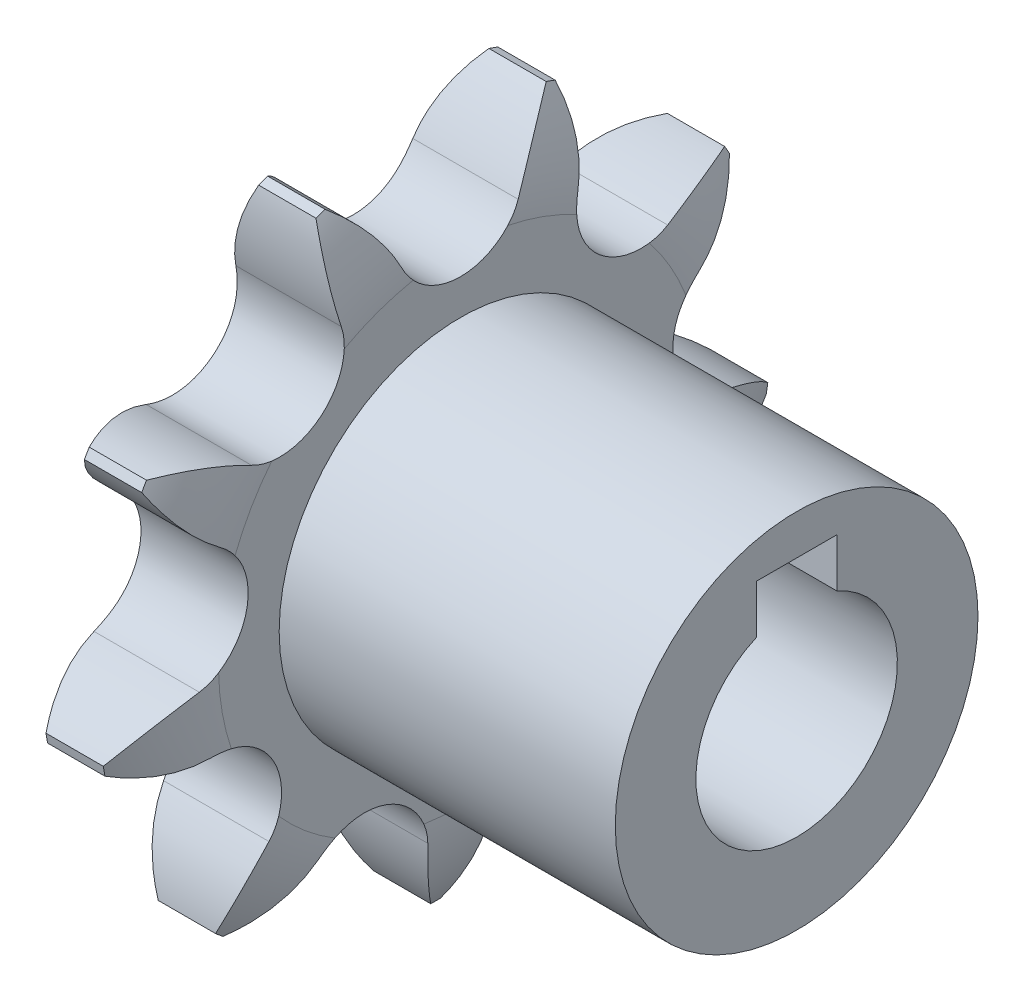
SolidWorks part; units mm, degrees
ref_plane "Plane1" through (0, 0, 0) normal (0, 0, 1) x (1, 0, 0)
ref_plane "Plane2" through (0, 0, 0) normal (0, 1, 0) x (1, 0, 0)
ref_plane "Plane3" through (0, 0, 0) normal (1, 0, 0) x (0, 0, -1)
sketch "Clipboard" plane through (0, 0, 0) normal (0, 1, 0) x (1, 0, 0)
  line L0 (0, 0) -> (9.4077, -1.49)
  line L1 (-15, 0) -> (100, 0) construction
  line L2 (0, 0) -> (-0.8203, 0.9272)
  line L3 (0, 0) -> (-8.8973, 3.4006)
  line L4 (0, 0) -> (3.0618, 0.4849)
  line L5 (0, 0) -> (-46.8476, -17.4728)
  line L6 (0, 0) -> (-4.4098, -2.9753)
  line L7 (-0.8203, 0.9272) -> (48.4205, 9.6097)
  line L8 (-76.2, 38.1) -> (-74.4, 38.1)
  line L9 (-73.3242, 40.7328) -> (-72.926, 40.7699)
  line L10 (-73.4529, 9.1872) -> (-63.2129, 9.1872)
  circle A0 centre (0, 0) radius 3.175
  circle A1 centre (0, 0) radius 8.4097
  circle A2 centre (0, 0) radius 37.5
  dimension "Num_teeth" = 9
  dimension "Thickness" = 5.3196
sketch "BasProSke" plane through (0, 0, 0) normal (0, 1, 0) x (1, 0, 0)
  line L0 (-10, 0) -> (60, 0) construction
  line L1 (0, 0) -> (0, 12.0069)
  line L2 (0, 0) -> (5.3196, 0)
  line L3 (5.3196, 0) -> (5.3196, 12.0069)
  line L4 (4.0816, 16.7027) -> (1.238, 16.7027)
  arc A0 (0, 12.0069) -> (1.238, 16.7027) centre (9.525, 12.0069) cw
  arc A1 (5.3196, 12.0069) -> (4.0816, 16.7027) centre (-4.2054, 12.0069) ccw
  dimension "D1" = 9.525
  dimension "Thickness" = 5.3196
  dimension "Diameter" = 33.4055
revolve "Base-Revolve" add sketch "BasProSke" angle 360 about L0
sketch "TooCutSke" plane through (0, 0, 0) normal (1, 0, 0) x (0, 0, -1)
  line L0 (0, 13.9564) -> (2.9063, 12.6011) construction
  line L1 (0, 0) -> (0, 107) construction
  line L2 (0, 13.9564) -> (-10, 13.9564) construction
  line L3 (0, 13.9564) -> (-2.9063, 12.6011) construction
  arc A0 (2.9063, 12.6011) -> (5.9941, 16.1247) centre (10.503, 9.0588) cw
  arc A1 (2.9063, 12.6011) -> (-2.9063, 12.6011) centre (0, 13.9564) cw
  arc A2 (-2.9063, 12.6011) -> (-5.9941, 16.1247) centre (-10.503, 9.0588) ccw
  arc A3 (5.9941, 16.1247) -> (-5.9941, 16.1247) centre (0, 0) ccw
extrude "ToothCut" cut sketch "TooCutSke" along normal through all
pattern_circular "TeethCuts" count 9 every 40 about axis through (-10, 0, 0) along (1, 0, 0) of "ToothCut"
sketch "HubNeaOneSke" plane through (0, 0, 0) normal (-1, 0, 0) x (0, 0, 1)
  circle A0 centre (0, 0) radius 8.4097
  dimension "Diameter" = 16.8193
extrude "HubNearOne" [suppressed] add sketch "HubNeaOneSke" along normal blind 44.6809
fillet "HubNearOneFillet" [suppressed] radius 0.4
sketch "HubNeaBotSke" plane through (0, 0, 0) normal (-1, 0, 0) x (0, 0, 1)
  circle A0 centre (0, 0) radius 8.4097
  dimension "Diameter" = 16.8193
extrude "HubNearBoth" [suppressed] add sketch "HubNeaBotSke" along normal blind 22.3405
fillet "HubNearBothFillet" [suppressed] radius 0.4
ref_plane "FarPln" through (5.3196, 0, 0) normal (1, 0, 0) x (0, 0, -1)
sketch "HubFarSke" plane through (5.3196, 0, 0) normal (1, 0, 0) x (0, 0, -1)
  circle A0 centre (0, 0) radius 8.4097
  dimension "Diameter" = 16.8193
extrude "HubFar" [suppressed] add sketch "HubFarSke" along normal blind 22.3405
fillet "HubFarFillet" [suppressed] radius 0.4
sketch "BorSke" plane through (0, 0, 0) normal (1, 0, 0) x (0, 0, -1)
  circle A0 centre (0, 0) radius 5
  dimension "Diameter" = 10
extrude "Bore" cut sketch "BorSke" along normal mid plane 100.001
sketch "KeySke" plane through (0, 0, 0) normal (1, 0, 0) x (0, 0, -1)
  line L0 (-2, 0) -> (-2, 6.8)
  line L1 (-2, 6.8) -> (2, 6.8)
  line L2 (2, 6.8) -> (2, 0)
  line L3 (0, 0) -> (0, 34) construction
  line L4 (-2, 0) -> (2, 0)
  dimension "Width" = 4
extrude "Keyway" [suppressed] cut sketch "KeySke" along normal mid plane 100.001
pattern_circular "Keyway2" [suppressed] count 2 every 90 about axis through (-10, 0, 0) along (1, 0, 0)
sketch "Sketch1" plane through (5.3196, 0, 0) normal (1, 0, 0) x (0, 0, -1)
  circle A0 centre (0, 0) radius 9
  circle A1 centre (0, 0) radius 3
  dimension "D1" = 18
  dimension "D2" = 6
extrude "Boss-Extrude1" add sketch "Sketch1" along normal offset from surface (16.6804 mm away) 22 up to face at (0, 0, -5)
sketch "Sketch2" plane through (0, 0, 0) normal (1, 0, 0) x (0, 0, -1)
  circle A0 centre (0, 0) radius 5
  dimension "D1" = 10
extrude "Cut-Extrude1" cut sketch "Sketch2" along normal blind 24
sketch "Sketch3" plane through (0, 0, 0) normal (-1, 0, 0) x (0, 0, 1)
  line L0 (-2, 7) -> (-2, 3)
  line L1 (-2, 7) -> (2, 7)
  line L2 (-2, 3) -> (2, 3)
  line L3 (2, 7) -> (2, 3)
  line L4 (-2, 7) -> (2, 3) construction
  line L5 (-2, 3) -> (2, 7) construction
  line L6 (0, 0) -> (0, 5) construction
  circle A0 centre (0, 0) radius 5 construction
  point P1 (0, 5)
  dimension "D1" = 4
  dimension "D2" = 4
extrude "Cut-Extrude2" cut sketch "Sketch3" against normal through all
equation "' \"Pitch@Clipboard\" = 12.7"
equation "' \"Num_strands@Clipboard\" = 1"
equation "' \"Num_teeth@Clipboard\" = 9"
equation "' \"Hub_dia@Clipboard\" = 50"
equation "' \"Overall_len@Clipboard\" = 3"
equation "' \"Diameter@BorSke\" = 12"
equation "' \"T_dim@Clipboard\" = 1"
equation "' \"Width@KeySke\" = 2"
equation "' \"Dr@Clipboard\" = 8.51"
equation "' \"Face_width@Clipboard\" = 7.2"
equation "' \"Side_radius@Clipboard\" = 12.7"
equation "' \"Side_relief@Clipboard\" = 1.27"
equation "' \"Transv_pitch@Clipboard\" = 13.92"
equation "' \"Show_teeth@Clipboard\" = 9"
equation "' \"Fillet_rad@Clipboard\" = 0.6"
equation "' \"Plate_wid@Clipboard\" = 11.8"
equation "\"Num_teeth@Clipboard\" = int( \"Num_teeth@Clipboard\" )"
equation "\"Num_teeth@Clipboard\" = ((sgn( \"Num_teeth@Clipboard\" - 5.0)+1)*( \"Num_teeth@Clipboard\" - 5.0))/2 +5.0"
equation "\"Num_teeth@Clipboard\" = ((sgn( \"Num_teeth@Clipboard\" - 200.0)-1)*( \"Num_teeth@Clipboard\" - 200.0))/-2 +200.0"
equation "\"MHD@Clipboard\" = \"Pitch@Clipboard\" * (1.0 / tan(3.14159265 / \"Num_teeth@Clipboard\" )) - 1.04 * \"Plate_wid@Clipboard\" - 0.76"
equation "\"Thickness@Clipboard\"  = \"Face_width@Clipboard\" + (\"Num_strands@Clipboard\" - 1) * \"Transv_pitch@Clipboard\""
equation "\"OAL@Clipboard\" = \"Thickness@Clipboard\" + 2 * \"Fillet_rad@Clipboard\" + 1"
equation "\"MHD@Clipboard\" = ((sgn( \"MHD@Clipboard\" - \"Hub_dia@Clipboard\" )-1)*( \"MHD@Clipboard\" - \"Hub_dia@Clipboard\" ))/-2+ \"Hub_dia@Clipboard\""
equation "\"OAL@Clipboard\" = ((sgn( \"OAL@Clipboard\" - \"Overall_len@Clipboard\" )+1)*( \"OAL@Clipboard\" - \"Overall_len@Clipboard\" ))/2 + \"Overall_len@Clipboard\" + 0.0005"
equation "\"Num_teeth@TeethCuts\" = int( \"Show_teeth@Clipboard\" ) + 1"
equation "\"Num_teeth@TeethCuts\" = ((sgn( \"Num_teeth@TeethCuts\" - \"Num_teeth@Clipboard\" )-1)*( \"Num_teeth@TeethCuts\" - \"Num_teeth@Clipboard\" ))/-2+ \"Num_teeth@Clipboard\""
equation "\"Num_teeth@TeethCuts\" = ((sgn( \"Num_teeth@TeethCuts\" - 2.0)+1)*( \"Num_teeth@TeethCuts\" - 2.0))/2 +2.0"
equation "\"Angle@TeethCuts\" = 360.0 / \"Num_teeth@Clipboard\""
equation "\"Seat_radius@TooCutSke\" = ( \"Pitch@Clipboard\" / 2.0) / sin(3.14159265 / \"Num_teeth@Clipboard\" ) - \"Dr@Clipboard\" / 2.0 + \"Dr@Clipboard\" * 0.505"
equation "\"R1@TooCutSke\"  = \"Dr@Clipboard\" * 0.505"
equation "\"X@TooCutSke\" = 140.0 - (90.0 / \"Num_teeth@Clipboard\")"
equation "\"R2@TooCutSke\" = 0.12 * \"Dr@Clipboard\" * ( \"Num_teeth@Clipboard\" + 2.0)"
equation "\"Overcut@TooCutSke\" = 0.5 + 0.625 * \"Pitch@Clipboard\" - 0.5 * \"Dr@Clipboard\"  +  \"Pitch@Clipboard\" / 2.0 / sin(3.14159265 / \"Num_teeth@Clipboard\" )"
equation "\"Diameter@BasProSke\" = 2.0 * ( 0.625 * \"Pitch@Clipboard\" - 0.5 * \"Dr@Clipboard\"  +  \"Pitch@Clipboard\" / 2.0 / sin(3.14159265 / \"Num_teeth@Clipboard\" ))"
equation "\"Thickness@BasProSke\"  = \"Thickness@Clipboard\""
equation "\"G1@BasProSke\" =  \"Side_relief@Clipboard\""
equation "\"G2@BasProSke\" =  \"Side_relief@Clipboard\""
equation "\"D1@BasProSke\" =  \"Side_radius@Clipboard\""
equation "\"Diameter@HubNeaOneSke\" = \"MHD@Clipboard\""
equation "\"Length@HubNearOne\" = \"OAL@Clipboard\" - \"Thickness@BasProSke\""
equation "\"Diameter@HubNeaBotSke\" = \"MHD@Clipboard\""
equation "\"Length@HubNearBoth\" = ( \"OAL@Clipboard\" - \"Thickness@BasProSke\" ) / 2.0"
equation "\"D1@HubNearOneFillet\" = \"Fillet_rad@Clipboard\""
equation "\"D1@HubNearBothFillet\" = \"Fillet_rad@Clipboard\""
equation "\"Thickness@FarPln\" = \"Thickness@BasProSke\""
equation "\"Diameter@HubFarSke\" = \"MHD@Clipboard\""
equation "\"Length@HubFar\" = ( \"OAL@Clipboard\" - \"Thickness@BasProSke\" ) / 2.0"
equation "\"D1@HubFarFillet\" = \"Fillet_rad@Clipboard\""
equation "\"D1@Bore\" = \"OAL@Clipboard\" * 2.0"
equation "\"D1@Keyway\" = \"OAL@Clipboard\" * 2.0"
equation "\"Offset@KeySke\" = \"T_dim@Clipboard\" + \"Diameter@BorSke\" / 2.0"
